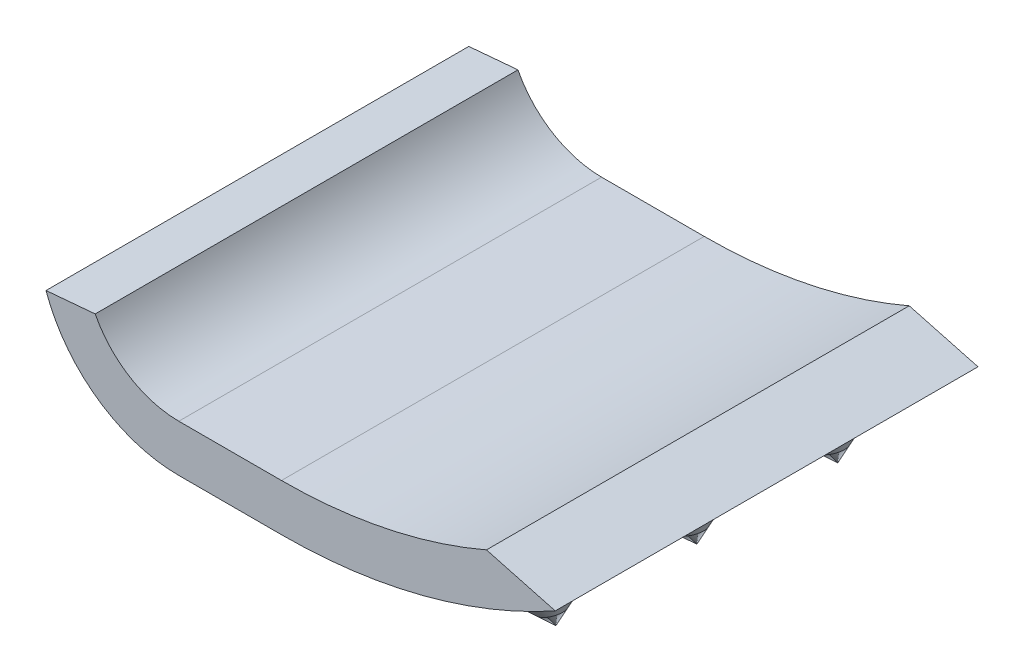
SolidWorks part; units mm, degrees
ref_plane "Front Plane" through (0, 0, 0) normal (0, 0, 1) x (1, 0, 0)
ref_plane "Top Plane" through (0, 0, 0) normal (0, 1, 0) x (1, 0, 0)
ref_plane "Right Plane" through (0, 0, 0) normal (1, 0, 0) x (0, 0, -1)
sketch "Sketch1" plane through (0, 0, 0) normal (0, 0, 1) x (1, 0, 0)
  line L0 (-1.7348, 0) -> (1.7348, 0)
  line L1 (-6.2229, 3.1691) -> (-4.5604, 3.3146)
  line L2 (10.9867, 2.3975) -> (8.6623, 3.0204)
  line L3 (-1.7348, 1.5875) -> (1.7348, 1.5875)
  arc A0 (-1.7348, 0) -> (-6.2229, 3.1691) centre (-1.7348, 4.7625) cw
  arc A1 (1.7348, 0) -> (10.9867, 2.3975) centre (1.7348, 19.05) ccw
  arc A2 (-1.7348, 1.5875) -> (-4.5604, 3.3146) centre (-1.7348, 4.7625) cw
  arc A3 (1.7348, 1.5875) -> (8.6623, 3.0204) centre (1.7348, 19.05) ccw
  point P4 (0, 0)
  dimension "D2" = 4.7625
  dimension "D5" = 19.05
  dimension "D1" = 3.4696
  dimension "D3" = 5
  dimension "D4" = 1.6688
  dimension "D6" = 15
  dimension "D7" = 1.5875
  dimension "D8" = 13.2227
extrude "Boss-Extrude1" add sketch "Sketch1" along normal blind 14.2875
sketch "Sketch2" plane through (0, 0, 0) normal (0, -1, 0) x (1, 0, 0)
  line L0 (-6.2229, 14.2875) -> (-6.2229, 0) construction
  circle A0 centre (0, 2.3812) radius 1.5875
  circle A1 centre (0, 7.1437) radius 1.5875
  circle A2 centre (0, 11.9062) radius 1.5875
  point P11 (-6.2229, 7.1437)
  dimension "D1" = 3.175
  dimension "D2" = 4.7625
  dimension "D3" = 4.7625
extrude "Boss-Extrude2" add sketch "Sketch2" along normal blind 1.5875
chamfer "Chamfer1" distance 1.5875 angle 45 3 edges at (0, -1.5875, 10.3187) (0, -1.5875, 5.5563) (0, -1.5875, 0.7937)
ref_plane "Plane1" through (-0.7527, -1.3038, 0) normal (-0.5, -0.866, 0) x (0, 0, -1)
sketch "Sketch3" plane through (-0.7527, -1.3038, 0) normal (-0.5, -0.866, 0) x (0, 0, -1)
  line L0 (-14.2875, -6.9737) -> (0, -6.9737) construction
  circle A0 centre (-2.3812, -3.7987) radius 1.5875
  circle A1 centre (-7.1437, -3.7987) radius 1.5875
  circle A2 centre (-11.9062, -3.7987) radius 1.5875
  point P9 (-7.1437, -6.9737)
  dimension "D1" = 3.175
  dimension "D2" = 4.7625
  dimension "D3" = 4.7625
  dimension "D4" = 3.175
extrude "Boss-Extrude3" add sketch "Sketch3" along normal blind 1.5875 and the other way blind 0.7937
chamfer "Chamfer2" distance 1.5875 angle 45 3 edges at (-3.4614, -1.573, 11.9062) (-3.4614, -1.573, 7.1437) (-3.4614, -1.573, 2.3812)
ref_plane "Plane2" through (0.0431, -0.3508, 0) normal (0.1219, -0.9925, 0) x (0, 0, -1)
sketch "Sketch5" plane through (0.0431, -0.3508, 0) normal (0.1219, -0.9925, 0) x (0, 0, -1)
  line L0 (-14.2875, 1.7219) -> (0, 1.7219) construction
  circle A0 centre (-7.1437, 4.1031) radius 1.5875
  circle A1 centre (-2.3812, 4.1031) radius 1.5875
  circle A2 centre (-11.9062, 4.1031) radius 1.5875
  point P10 (-7.1437, 1.7219)
  dimension "D1" = 3.175
  dimension "D2" = 4.7625
  dimension "D3" = 4.7625
  dimension "D4" = 2.3812
extrude "Boss-Extrude4" add sketch "Sketch5" along normal blind 1.5875 and the other way blind 0.7937 separate body
chamfer "Chamfer3" distance 1.5875 angle 45 1 edges at (5.8848, -1.2329, 11.9062)
chamfer "Chamfer4" distance 1.5875 angle 45 1 edges at (5.8848, -1.2329, 7.1437)
chamfer "Chamfer5" distance 1.5875 angle 45 1 edges at (5.8848, -1.2329, 2.3812)
ref_plane "Plane3" through (0.5959, -1.6371, 0) normal (0.342, -0.9397, 0) x (0, 0, -1)
sketch "Sketch6" plane through (0.5959, -1.6371, 0) normal (0.342, -0.9397, 0) x (0, 0, -1)
  line L0 (-14.2875, 11.1442) -> (0, 11.1442) construction
  circle A0 centre (-11.9062, 7.9692) radius 1.5875
  circle A1 centre (-7.1437, 7.9692) radius 1.5875
  circle A2 centre (-2.3812, 7.9692) radius 1.5875
  point P10 (-7.1437, 11.1442)
  dimension "D1" = 3.175
  dimension "D2" = 4.7625
  dimension "D3" = 4.7625
  dimension "D4" = 3.175
extrude "Boss-Extrude5" add sketch "Sketch6" along normal blind 1.5875 and the other way blind 0.7937
chamfer "Chamfer6" distance 1.5875 angle 45 3 edges at (10.1192, 0.1397, 2.3812) (10.1192, 0.1397, 7.1437) (10.1192, 0.1397, 11.9062)
